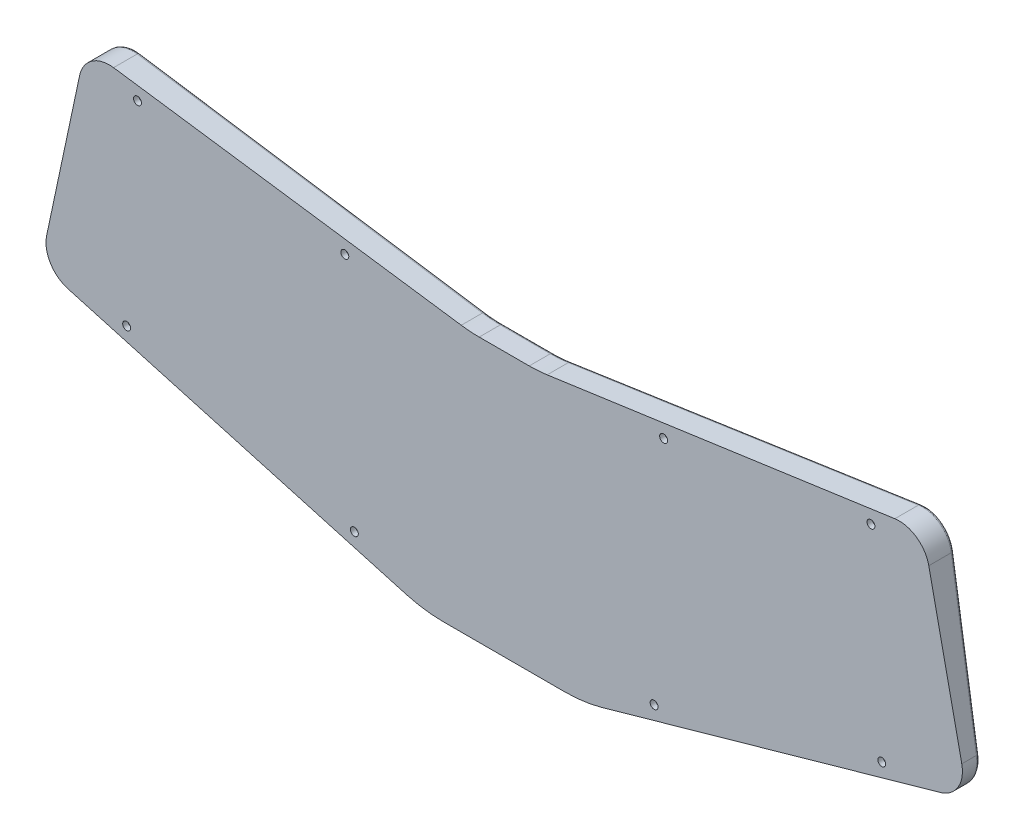
SolidWorks part; units mm, degrees
ref_plane "Front Plane" through (0, 0, 0) normal (0, 0, 1) x (1, 0, 0)
ref_plane "Top Plane" through (0, 0, 0) normal (0, 1, 0) x (1, 0, 0)
ref_plane "Right Plane" through (0, 0, 0) normal (1, 0, 0) x (0, 0, -1)
sketch "Model" plane through (0, 0, 0) normal (0, 0, 1) x (1, 0, 0)
  line L0 (7.1929, 63.9009) -> (19.4198, 61.302)
  line L1 (19.9974, 60.4125) -> (17.3986, 48.1856)
  line L2 (16.509, 47.6079) -> (4.2822, 50.2068)
  line L3 (3.7045, 51.0964) -> (6.3034, 63.3232)
  line L4 (3.2426, 45.3161) -> (15.4694, 42.7172)
  line L5 (16.0471, 41.8276) -> (13.4482, 29.6008)
  line L6 (12.5587, 29.0231) -> (0.3318, 31.622)
  line L7 (-0.2458, 32.5116) -> (2.3531, 44.7384)
  line L8 (-0.7077, 26.7313) -> (11.5191, 24.1324)
  line L9 (12.0968, 23.2428) -> (9.4979, 11.016)
  line L10 (8.6084, 10.4383) -> (-3.6185, 13.0372)
  line L11 (-4.1962, 13.9268) -> (-1.5973, 26.1536)
  line L12 (26.1936, 61.9069) -> (38.4204, 59.308)
  line L13 (38.9981, 58.4184) -> (36.3992, 46.1916)
  line L14 (35.5096, 45.6139) -> (23.2828, 48.2128)
  line L15 (22.7051, 49.1023) -> (25.304, 61.3292)
  line L16 (22.2432, 43.3221) -> (34.4701, 40.7232)
  line L17 (35.0478, 39.8336) -> (32.4489, 27.6068)
  line L18 (31.5593, 27.0291) -> (19.3325, 29.628)
  line L19 (18.7548, 30.5175) -> (21.3537, 42.7444)
  line L20 (18.2929, 24.7373) -> (30.5198, 22.1384)
  line L21 (31.0974, 21.2488) -> (28.4985, 9.022)
  line L22 (27.609, 8.4443) -> (15.3821, 11.0432)
  line L23 (14.8045, 11.9327) -> (17.4034, 24.1596)
  line L24 (45.2981, 60.4019) -> (57.525, 57.803)
  line L25 (58.1027, 56.9135) -> (55.5038, 44.6866)
  line L26 (54.6142, 44.109) -> (42.3874, 46.7078)
  line L27 (41.8097, 47.5974) -> (44.4086, 59.8242)
  line L28 (41.3478, 41.8171) -> (53.5747, 39.2182)
  line L29 (54.1523, 38.3287) -> (51.5534, 26.1018)
  line L30 (50.6639, 25.5241) -> (38.4371, 28.123)
  line L31 (37.8594, 29.0126) -> (40.4583, 41.2394)
  line L32 (37.3975, 23.2323) -> (49.6243, 20.6334)
  line L33 (50.202, 19.7439) -> (47.6031, 7.517)
  line L34 (46.7136, 6.9393) -> (34.4867, 9.5382)
  line L35 (33.9091, 10.4278) -> (36.5079, 22.6546)
  line L36 (64.4027, 58.897) -> (76.6296, 56.2981)
  line L37 (77.2072, 55.4085) -> (74.6083, 43.1817)
  line L38 (73.7188, 42.604) -> (61.492, 45.2029)
  line L39 (60.9143, 46.0924) -> (63.5132, 58.3193)
  line L40 (60.4524, 40.3122) -> (72.6792, 37.7133)
  line L41 (73.2569, 36.8237) -> (70.658, 24.5969)
  line L42 (69.7685, 24.0192) -> (57.5416, 26.6181)
  line L43 (56.964, 27.5076) -> (59.5629, 39.7345)
  line L44 (56.5021, 21.7274) -> (68.7289, 19.1285)
  line L45 (69.3066, 18.2389) -> (66.7077, 6.0121)
  line L46 (65.8182, 5.4344) -> (53.5913, 8.0333)
  line L47 (53.0136, 8.9228) -> (55.6125, 21.1497)
  line L48 (52.5518, 3.1425) -> (64.7786, 0.5437)
  line L49 (65.3563, -0.3459) -> (62.7574, -12.5727)
  line L50 (61.8678, -13.1504) -> (49.641, -10.5515)
  line L51 (49.0633, -9.662) -> (51.6622, 2.5649)
  line L52 (82.4677, 52.5013) -> (94.6946, 49.9024)
  line L53 (95.2723, 49.0128) -> (92.6734, 36.786)
  line L54 (91.7838, 36.2083) -> (79.557, 38.8072)
  line L55 (78.9793, 39.6967) -> (81.5782, 51.9236)
  line L56 (78.5174, 33.9165) -> (90.7443, 31.3176)
  line L57 (91.3219, 30.428) -> (88.723, 18.2012)
  line L58 (87.8335, 17.6235) -> (75.6067, 20.2224)
  line L59 (75.029, 21.1119) -> (77.6279, 33.3388)
  line L60 (74.5671, 15.3317) -> (86.7939, 12.7328)
  line L61 (87.3716, 11.8432) -> (84.7727, -0.3836)
  line L62 (83.8832, -0.9613) -> (71.6563, 1.6376)
  line L63 (71.0787, 2.5271) -> (73.6776, 14.754)
  line L64 (101.4684, 50.5072) -> (113.6952, 47.9083)
  line L65 (114.2729, 47.0188) -> (111.674, 34.792)
  line L66 (110.7845, 34.2143) -> (98.5576, 36.8132)
  line L67 (97.9799, 37.7027) -> (100.5788, 49.9296)
  line L68 (97.5181, 31.9224) -> (109.7449, 29.3235)
  line L69 (110.3226, 28.434) -> (107.7237, 16.2072)
  line L70 (106.8341, 15.6295) -> (94.6073, 18.2284)
  line L71 (94.0296, 19.1179) -> (96.6285, 31.3448)
  line L72 (93.5677, 13.3376) -> (105.7946, 10.7387)
  line L73 (106.3723, 9.8492) -> (103.7734, -2.3777)
  line L74 (102.8838, -2.9553) -> (90.657, -0.3564)
  line L75 (90.0793, 0.5331) -> (92.6782, 12.76)
  line L76 (134.1052, 48.9374) -> (131.5063, 36.7105)
  line L77 (130.6167, 36.1328) -> (118.3899, 38.7317)
  line L78 (117.8122, 39.6213) -> (120.4111, 51.8481)
  line L79 (117.3503, 33.841) -> (129.5772, 31.2421)
  line L80 (130.1548, 30.3526) -> (127.556, 18.1257)
  line L81 (126.6664, 17.548) -> (114.4396, 20.1469)
  line L82 (113.8619, 21.0365) -> (116.4608, 33.2633)
  line L83 (113.4, 15.2562) -> (125.6268, 12.6573)
  line L84 (126.2045, 11.7678) -> (123.6056, -0.4591)
  line L85 (122.7161, -1.0368) -> (110.4892, 1.5621)
  line L86 (109.9116, 2.4517) -> (112.5105, 14.6785)
  line L87 (70.6168, -3.2531) -> (82.8436, -5.852)
  line L88 (83.4213, -6.7416) -> (80.8224, -18.9684)
  line L89 (79.9329, -19.5461) -> (67.706, -16.9472)
  line L90 (67.1283, -16.0577) -> (69.7272, -3.8308)
  line L91 (89.6174, -5.2472) -> (101.8443, -7.8461)
  line L92 (102.4219, -8.7356) -> (99.823, -20.9625)
  line L93 (98.9335, -21.5401) -> (86.7066, -18.9412)
  line L94 (86.129, -18.0517) -> (88.7279, -5.8248)
  line L95 (117.654, -29.3648) -> (112.0852, -26.5274)
  line L96 (111.7574, -25.5186) -> (117.4323, -14.381)
  line L97 (118.4411, -14.0533) -> (129.5787, -19.7282)
  line L98 (129.9064, -20.7369) -> (124.2315, -31.8745)
  line L99 (123.2228, -32.2023) -> (117.654, -29.3648)
  line L100 (112.629, -33.5493) -> (124.2783, -36.8388)
  line L101 (137.0504, -38.6074) -> (160.1264, -38.6074)
  line L102 (160.1264, -38.6074) -> (183.2025, -38.6074)
  line L103 (195.9746, -36.8388) -> (207.6239, -33.5493)
  line L104 (226.4824, -28.2242) -> (271.949, -15.3856)
  line L105 (271.949, -15.3856) -> (293.9202, -9.1816)
  line L106 (210.7632, 57.9332) -> (177.0346, 53.1572)
  line L107 (169.604, 52.6338) -> (150.6488, 52.6338)
  line L108 (143.2182, 53.1572) -> (109.4896, 57.9332)
  line L109 (90.0873, 60.6806) -> (30.9176, 69.0589)
  line L110 (289.3352, 69.0589) -> (230.1656, 60.6806)
  line L111 (26.3327, -9.1816) -> (48.3039, -15.3856)
  line L112 (48.3039, -15.3856) -> (93.7705, -28.2242)
  line L113 (312.7787, -3.8564) -> (324.1811, -0.6367)
  line L114 (-2.1254, 39.3007) -> (3.622, 66.34)
  line L115 (-2.1254, 39.3007) -> (-8.8731, 7.5553)
  line L116 (13.8071, 71.4818) -> (11.4504, 71.8155)
  line L117 (-3.9283, -0.6367) -> (7.4742, -3.8564)
  line L118 (306.4458, 71.4818) -> (308.8024, 71.8155)
  line L119 (322.3782, 39.3007) -> (329.1259, 7.5553)
  line L120 (322.3782, 39.3007) -> (316.6308, 66.34)
  line L121 (121.3006, 52.4258) -> (133.5275, 49.8269)
  line L122 (313.0599, 63.9009) -> (300.8331, 61.302)
  line L123 (300.2554, 60.4125) -> (302.8543, 48.1856)
  line L124 (303.7438, 47.6079) -> (315.9707, 50.2068)
  line L125 (316.5483, 51.0964) -> (313.9494, 63.3232)
  line L126 (317.0102, 45.3161) -> (304.7834, 42.7172)
  line L127 (304.2057, 41.8276) -> (306.8046, 29.6008)
  line L128 (307.6941, 29.0231) -> (319.921, 31.622)
  line L129 (320.4987, 32.5116) -> (317.8998, 44.7384)
  line L130 (320.9605, 26.7313) -> (308.7337, 24.1324)
  line L131 (308.156, 23.2428) -> (310.7549, 11.016)
  line L132 (311.6445, 10.4383) -> (323.8713, 13.0372)
  line L133 (324.449, 13.9268) -> (321.8501, 26.1536)
  line L134 (294.0593, 61.9069) -> (281.8324, 59.308)
  line L135 (281.2548, 58.4184) -> (283.8536, 46.1916)
  line L136 (284.7432, 45.6139) -> (296.97, 48.2128)
  line L137 (297.5477, 49.1023) -> (294.9488, 61.3292)
  line L138 (298.0096, 43.3221) -> (285.7828, 40.7232)
  line L139 (285.2051, 39.8336) -> (287.804, 27.6068)
  line L140 (288.6935, 27.0291) -> (300.9204, 29.628)
  line L141 (301.498, 30.5175) -> (298.8991, 42.7444)
  line L142 (301.9599, 24.7373) -> (289.7331, 22.1384)
  line L143 (289.1554, 21.2488) -> (291.7543, 9.022)
  line L144 (292.6438, 8.4443) -> (304.8707, 11.0432)
  line L145 (305.4484, 11.9327) -> (302.8495, 24.1596)
  line L146 (274.9547, 60.4019) -> (262.7278, 57.803)
  line L147 (262.1502, 56.9135) -> (264.7491, 44.6866)
  line L148 (265.6386, 44.109) -> (277.8655, 46.7078)
  line L149 (278.4431, 47.5974) -> (275.8442, 59.8242)
  line L150 (278.905, 41.8171) -> (266.6782, 39.2182)
  line L151 (266.1005, 38.3287) -> (268.6994, 26.1018)
  line L152 (269.5889, 25.5241) -> (281.8158, 28.123)
  line L153 (282.3935, 29.0126) -> (279.7946, 41.2394)
  line L154 (282.8553, 23.2323) -> (270.6285, 20.6334)
  line L155 (270.0508, 19.7439) -> (272.6497, 7.517)
  line L156 (273.5393, 6.9393) -> (285.7661, 9.5382)
  line L157 (286.3438, 10.4278) -> (283.7449, 22.6546)
  line L158 (255.8501, 58.897) -> (243.6233, 56.2981)
  line L159 (243.0456, 55.4085) -> (245.6445, 43.1817)
  line L160 (246.534, 42.604) -> (258.7609, 45.2029)
  line L161 (259.3385, 46.0924) -> (256.7397, 58.3193)
  line L162 (259.8004, 40.3122) -> (247.5736, 37.7133)
  line L163 (246.9959, 36.8237) -> (249.5948, 24.5969)
  line L164 (250.4843, 24.0192) -> (262.7112, 26.6181)
  line L165 (263.2889, 27.5076) -> (260.69, 39.7345)
  line L166 (263.7508, 21.7274) -> (251.5239, 19.1285)
  line L167 (250.9462, 18.2389) -> (253.5451, 6.0121)
  line L168 (254.4347, 5.4344) -> (266.6615, 8.0333)
  line L169 (267.2392, 8.9228) -> (264.6403, 21.1497)
  line L170 (267.7011, 3.1425) -> (255.4742, 0.5437)
  line L171 (254.8966, -0.3459) -> (257.4954, -12.5727)
  line L172 (258.385, -13.1504) -> (270.6118, -10.5515)
  line L173 (271.1895, -9.662) -> (268.5906, 2.5649)
  line L174 (237.7851, 52.5013) -> (225.5582, 49.9024)
  line L175 (224.9806, 49.0128) -> (227.5795, 36.786)
  line L176 (228.469, 36.2083) -> (240.6958, 38.8072)
  line L177 (241.2735, 39.6967) -> (238.6746, 51.9236)
  line L178 (241.7354, 33.9165) -> (229.5086, 31.3176)
  line L179 (228.9309, 30.428) -> (231.5298, 18.2012)
  line L180 (232.4193, 17.6235) -> (244.6462, 20.2224)
  line L181 (245.2238, 21.1119) -> (242.6249, 33.3388)
  line L182 (245.6857, 15.3317) -> (233.4589, 12.7328)
  line L183 (232.8812, 11.8432) -> (235.4801, -0.3836)
  line L184 (236.3696, -0.9613) -> (248.5965, 1.6376)
  line L185 (249.1742, 2.5271) -> (246.5753, 14.754)
  line L186 (218.7845, 50.5072) -> (206.5576, 47.9083)
  line L187 (205.9799, 47.0188) -> (208.5788, 34.792)
  line L188 (209.4684, 34.2143) -> (221.6952, 36.8132)
  line L189 (222.2729, 37.7027) -> (219.674, 49.9296)
  line L190 (222.7348, 31.9224) -> (210.5079, 29.3235)
  line L191 (209.9303, 28.434) -> (212.5292, 16.2072)
  line L192 (213.4187, 15.6295) -> (225.6455, 18.2284)
  line L193 (226.2232, 19.1179) -> (223.6243, 31.3448)
  line L194 (226.6851, 13.3376) -> (214.4583, 10.7387)
  line L195 (213.8806, 9.8492) -> (216.4795, -2.3777)
  line L196 (217.369, -2.9553) -> (229.5959, -0.3564)
  line L197 (230.1735, 0.5331) -> (227.5746, 12.76)
  line L198 (186.1477, 48.9374) -> (188.7466, 36.7105)
  line L199 (189.6361, 36.1328) -> (201.8629, 38.7317)
  line L200 (202.4406, 39.6213) -> (199.8417, 51.8481)
  line L201 (202.9025, 33.841) -> (190.6757, 31.2421)
  line L202 (190.098, 30.3526) -> (192.6969, 18.1257)
  line L203 (193.5864, 17.548) -> (205.8133, 20.1469)
  line L204 (206.3909, 21.0365) -> (203.792, 33.2633)
  line L205 (206.8528, 15.2562) -> (194.626, 12.6573)
  line L206 (194.0483, 11.7678) -> (196.6472, -0.4591)
  line L207 (197.5367, -1.0368) -> (209.7636, 1.5621)
  line L208 (210.3413, 2.4517) -> (207.7424, 14.6785)
  line L209 (249.636, -3.2531) -> (237.4092, -5.852)
  line L210 (236.8315, -6.7416) -> (239.4304, -18.9684)
  line L211 (240.32, -19.5461) -> (252.5468, -16.9472)
  line L212 (253.1245, -16.0577) -> (250.5256, -3.8308)
  line L213 (230.6354, -5.2472) -> (218.4086, -7.8461)
  line L214 (217.8309, -8.7356) -> (220.4298, -20.9625)
  line L215 (221.3193, -21.5401) -> (233.5462, -18.9412)
  line L216 (234.1239, -18.0517) -> (231.525, -5.8248)
  line L217 (202.5988, -29.3648) -> (208.1676, -26.5274)
  line L218 (208.4954, -25.5186) -> (202.8205, -14.381)
  line L219 (201.8118, -14.0533) -> (190.6742, -19.7282)
  line L220 (190.3464, -20.7369) -> (196.0213, -31.8745)
  line L221 (197.03, -32.2023) -> (202.5988, -29.3648)
  line L222 (198.9522, 52.4258) -> (186.7253, 49.8269)
  line L223 (169.604, 55.6338) -> (150.6488, 55.6338)
  line L224 (143.6388, 56.1276) -> (11.8711, 74.7858)
  line L225 (0.6876, 66.9637) -> (-5.0598, 39.9244)
  line L226 (-5.0598, 39.9244) -> (-11.8075, 8.179)
  line L227 (-4.7435, -3.5238) -> (47.4886, -18.2727)
  line L228 (47.4886, -18.2727) -> (123.463, -39.7259)
  line L229 (137.0504, -41.6074) -> (160.1264, -41.6074)
  line L230 (160.1264, -41.6074) -> (183.2025, -41.6074)
  line L231 (196.7898, -39.7259) -> (272.7642, -18.2727)
  line L232 (272.7642, -18.2727) -> (324.9963, -3.5238)
  line L233 (332.0603, 8.179) -> (325.3126, 39.9244)
  line L234 (325.3126, 39.9244) -> (319.5653, 66.9637)
  line L235 (308.3818, 74.7858) -> (176.614, 56.1276)
  line L236 (169.604, 57.1338) -> (150.6488, 57.1338)
  line L237 (143.8491, 57.6128) -> (12.0814, 76.271)
  line L238 (-0.7797, 67.2756) -> (-6.527, 40.2363)
  line L239 (-6.527, 40.2363) -> (-13.2747, 8.4909)
  line L240 (-5.1511, -4.9673) -> (47.081, -19.7163)
  line L241 (47.081, -19.7163) -> (123.0554, -41.1694)
  line L242 (137.0504, -43.1074) -> (160.1264, -43.1074)
  line L243 (160.1264, -43.1074) -> (183.2025, -43.1074)
  line L244 (197.1974, -41.1694) -> (273.1718, -19.7163)
  line L245 (273.1718, -19.7163) -> (325.404, -4.9673)
  line L246 (333.5276, 8.4909) -> (326.7799, 40.2363)
  line L247 (326.7799, 40.2363) -> (321.0325, 67.2756)
  line L248 (308.1715, 76.271) -> (176.4037, 57.6128)
  arc A0 (106.6702, -28.8979) -> (101.2821, -27.3764) centre (103.1997, -30.8868) ccw
  arc A1 (93.7705, -28.2242) -> (101.2821, -27.3764) centre (96.4879, -18.6005) ccw
  arc A2 (106.6702, -28.8979) -> (112.629, -33.5493) centre (115.3464, -23.9256) ccw
  circle A3 centre (103.3356, -30.4056) radius 1.5
  arc A4 (207.6239, -33.5493) -> (213.5826, -28.8979) centre (204.9064, -23.9256) ccw
  arc A5 (218.9708, -27.3764) -> (226.4824, -28.2242) centre (223.7649, -18.6005) ccw
  arc A6 (218.9708, -27.3764) -> (213.5826, -28.8979) centre (217.0531, -30.8868) ccw
  circle A7 centre (216.9173, -30.4056) radius 1.5
  arc A8 (218.0932, 56.0855) -> (223.6367, 56.8704) centre (220.4644, 59.3069) ccw
  arc A9 (96.6161, 56.8704) -> (102.1596, 56.0855) centre (99.7884, 59.3069) ccw
  arc A10 (109.4896, 57.9332) -> (102.1596, 56.0855) centre (108.0876, 48.032) ccw
  arc A11 (96.6161, 56.8704) -> (90.0873, 60.6806) centre (88.6852, 50.7793) ccw
  arc A12 (218.0932, 56.0855) -> (210.7632, 57.9332) centre (212.1652, 48.032) ccw
  arc A13 (230.1656, 60.6806) -> (223.6367, 56.8704) centre (231.5676, 50.7793) ccw
  circle A14 centre (99.7183, 58.8118) radius 1.5
  circle A15 centre (220.5345, 58.8118) radius 1.5
  arc A16 (305.2671, -3.0086) -> (299.8789, -4.5301) centre (303.3494, -6.519) ccw
  arc A17 (20.3739, -4.5301) -> (14.9858, -3.0086) centre (16.9034, -6.519) ccw
  arc A18 (20.3739, -4.5301) -> (26.3327, -9.1816) centre (29.0501, 0.4421) ccw
  arc A19 (305.2671, -3.0086) -> (312.7787, -3.8564) centre (310.0612, 5.7673) ccw
  arc A20 (293.9202, -9.1816) -> (299.8789, -4.5301) centre (291.2027, 0.4421) ccw
  arc A21 (7.4742, -3.8564) -> (14.9858, -3.0086) centre (10.1916, 5.7673) ccw
  circle A22 centre (17.0393, -6.0378) radius 1.5
  circle A23 centre (303.2135, -6.0378) radius 1.5
  arc A24 (-8.8731, 7.5553) -> (-3.9283, -0.6367) centre (-2.026, 6.0999) ccw
  arc A25 (11.4504, 71.8155) -> (3.622, 66.34) centre (10.469, 64.8846) ccw
  arc A26 (316.6308, 66.34) -> (308.8024, 71.8155) centre (309.7838, 64.8846) ccw
  arc A27 (324.1811, -0.6367) -> (329.1259, 7.5553) centre (322.2789, 6.0999) ccw
  arc A28 (296.6652, 67.2112) -> (302.641, 68.6986) centre (299.0364, 70.4326) ccw
  arc A29 (17.6118, 68.6986) -> (23.5876, 67.2112) centre (21.2165, 70.4326) ccw
  arc A30 (30.9176, 69.0589) -> (23.5876, 67.2112) centre (29.5156, 59.1577) ccw
  arc A31 (17.6118, 68.6986) -> (13.8071, 71.4818) centre (13.106, 66.5312) ccw
  arc A32 (306.4458, 71.4818) -> (302.641, 68.6986) centre (307.1468, 66.5312) ccw
  arc A33 (296.6652, 67.2112) -> (289.3352, 69.0589) centre (290.7372, 59.1577) ccw
  circle A34 centre (299.1065, 69.9376) radius 1.5
  circle A35 centre (21.1464, 69.9376) radius 1.5
  arc A36 (3.7045, 51.0964) -> (4.2822, 50.2068) centre (4.4381, 50.9404) ccw
  arc A37 (7.1929, 63.9009) -> (6.3034, 63.3232) centre (7.037, 63.1673) ccw
  arc A38 (19.9974, 60.4125) -> (19.4198, 61.302) centre (19.2638, 60.5684) ccw
  arc A39 (16.509, 47.6079) -> (17.3986, 48.1856) centre (16.6649, 48.3415) ccw
  arc A40 (3.2426, 45.3161) -> (2.3531, 44.7384) centre (3.0867, 44.5825) ccw
  arc A41 (-0.2458, 32.5116) -> (0.3318, 31.622) centre (0.4878, 32.3556) ccw
  arc A42 (12.5587, 29.0231) -> (13.4482, 29.6008) centre (12.7146, 29.7567) ccw
  arc A43 (16.0471, 41.8276) -> (15.4694, 42.7172) centre (15.3135, 41.9836) ccw
  arc A44 (-0.7077, 26.7313) -> (-1.5973, 26.1536) centre (-0.8637, 25.9977) ccw
  arc A45 (-4.1962, 13.9268) -> (-3.6185, 13.0372) centre (-3.4625, 13.7708) ccw
  arc A46 (8.6084, 10.4383) -> (9.4979, 11.016) centre (8.7643, 11.1719) ccw
  arc A47 (12.0968, 23.2428) -> (11.5191, 24.1324) centre (11.3632, 23.3988) ccw
  arc A48 (14.8045, 11.9327) -> (15.3821, 11.0432) centre (15.5381, 11.7768) ccw
  arc A49 (27.609, 8.4443) -> (28.4985, 9.022) centre (27.7649, 9.1779) ccw
  arc A50 (31.0974, 21.2488) -> (30.5198, 22.1384) centre (30.3638, 21.4048) ccw
  arc A51 (18.2929, 24.7373) -> (17.4034, 24.1596) centre (18.137, 24.0036) ccw
  arc A52 (18.7548, 30.5175) -> (19.3325, 29.628) centre (19.4884, 30.3616) ccw
  arc A53 (31.5593, 27.0291) -> (32.4489, 27.6068) centre (31.7152, 27.7627) ccw
  arc A54 (35.0478, 39.8336) -> (34.4701, 40.7232) centre (34.3141, 39.9896) ccw
  arc A55 (22.2432, 43.3221) -> (21.3537, 42.7444) centre (22.0873, 42.5885) ccw
  arc A56 (22.7051, 49.1023) -> (23.2828, 48.2128) centre (23.4387, 48.9464) ccw
  arc A57 (35.5096, 45.6139) -> (36.3992, 46.1916) centre (35.6656, 46.3475) ccw
  arc A58 (38.9981, 58.4184) -> (38.4204, 59.308) centre (38.2645, 58.5744) ccw
  arc A59 (26.1936, 61.9069) -> (25.304, 61.3292) centre (26.0376, 61.1733) ccw
  arc A60 (33.9091, 10.4278) -> (34.4867, 9.5382) centre (34.6427, 10.2718) ccw
  arc A61 (37.3975, 23.2323) -> (36.5079, 22.6546) centre (37.2416, 22.4987) ccw
  arc A62 (50.202, 19.7439) -> (49.6243, 20.6334) centre (49.4684, 19.8998) ccw
  arc A63 (46.7136, 6.9393) -> (47.6031, 7.517) centre (46.8695, 7.673) ccw
  arc A64 (50.6639, 25.5241) -> (51.5534, 26.1018) centre (50.8198, 26.2578) ccw
  arc A65 (37.8594, 29.0126) -> (38.4371, 28.123) centre (38.593, 28.8567) ccw
  arc A66 (41.3478, 41.8171) -> (40.4583, 41.2394) centre (41.1919, 41.0835) ccw
  arc A67 (54.1523, 38.3287) -> (53.5747, 39.2182) centre (53.4187, 38.4846) ccw
  arc A68 (54.6142, 44.109) -> (55.5038, 44.6866) centre (54.7702, 44.8426) ccw
  arc A69 (41.8097, 47.5974) -> (42.3874, 46.7078) centre (42.5433, 47.4415) ccw
  arc A70 (45.2981, 60.4019) -> (44.4086, 59.8242) centre (45.1422, 59.6683) ccw
  arc A71 (58.1027, 56.9135) -> (57.525, 57.803) centre (57.369, 57.0694) ccw
  arc A72 (56.964, 27.5076) -> (57.5416, 26.6181) centre (57.6976, 27.3517) ccw
  arc A73 (60.4524, 40.3122) -> (59.5629, 39.7345) centre (60.2965, 39.5785) ccw
  arc A74 (73.2569, 36.8237) -> (72.6792, 37.7133) centre (72.5233, 36.9797) ccw
  arc A75 (69.7685, 24.0192) -> (70.658, 24.5969) centre (69.9244, 24.7528) ccw
  arc A76 (60.9143, 46.0924) -> (61.492, 45.2029) centre (61.6479, 45.9365) ccw
  arc A77 (73.7188, 42.604) -> (74.6083, 43.1817) centre (73.8747, 43.3376) ccw
  arc A78 (77.2072, 55.4085) -> (76.6296, 56.2981) centre (76.4736, 55.5645) ccw
  arc A79 (64.4027, 58.897) -> (63.5132, 58.3193) centre (64.2468, 58.1634) ccw
  arc A80 (53.0136, 8.9228) -> (53.5913, 8.0333) centre (53.7472, 8.7669) ccw
  arc A81 (56.5021, 21.7274) -> (55.6125, 21.1497) centre (56.3461, 20.9937) ccw
  arc A82 (69.3066, 18.2389) -> (68.7289, 19.1285) centre (68.573, 18.3948) ccw
  arc A83 (65.8182, 5.4344) -> (66.7077, 6.0121) centre (65.9741, 6.168) ccw
  arc A84 (49.0633, -9.662) -> (49.641, -10.5515) centre (49.7969, -9.8179) ccw
  arc A85 (52.5518, 3.1425) -> (51.6622, 2.5649) centre (52.3958, 2.4089) ccw
  arc A86 (65.3563, -0.3459) -> (64.7786, 0.5437) centre (64.6227, -0.19) ccw
  arc A87 (61.8678, -13.1504) -> (62.7574, -12.5727) centre (62.0238, -12.4168) ccw
  arc A88 (67.1283, -16.0577) -> (67.706, -16.9472) centre (67.8619, -16.2136) ccw
  arc A89 (70.6168, -3.2531) -> (69.7272, -3.8308) centre (70.4608, -3.9868) ccw
  arc A90 (83.4213, -6.7416) -> (82.8436, -5.852) centre (82.6877, -6.5856) ccw
  arc A91 (79.9329, -19.5461) -> (80.8224, -18.9684) centre (80.0888, -18.8125) ccw
  arc A92 (71.0787, 2.5271) -> (71.6563, 1.6376) centre (71.8123, 2.3712) ccw
  arc A93 (83.8832, -0.9613) -> (84.7727, -0.3836) centre (84.0391, -0.2277) ccw
  arc A94 (87.3716, 11.8432) -> (86.7939, 12.7328) centre (86.638, 11.9992) ccw
  arc A95 (74.5671, 15.3317) -> (73.6776, 14.754) centre (74.4112, 14.5981) ccw
  arc A96 (75.029, 21.1119) -> (75.6067, 20.2224) centre (75.7626, 20.956) ccw
  arc A97 (87.8335, 17.6235) -> (88.723, 18.2012) centre (87.9894, 18.3571) ccw
  arc A98 (91.3219, 30.428) -> (90.7443, 31.3176) centre (90.5883, 30.584) ccw
  arc A99 (78.5174, 33.9165) -> (77.6279, 33.3388) centre (78.3615, 33.1829) ccw
  arc A100 (78.9793, 39.6967) -> (79.557, 38.8072) centre (79.7129, 39.5408) ccw
  arc A101 (82.4677, 52.5013) -> (81.5782, 51.9236) centre (82.3118, 51.7677) ccw
  arc A102 (95.2723, 49.0128) -> (94.6946, 49.9024) centre (94.5387, 49.1688) ccw
  arc A103 (91.7838, 36.2083) -> (92.6734, 36.786) centre (91.9398, 36.9419) ccw
  arc A104 (97.9799, 37.7027) -> (98.5576, 36.8132) centre (98.7135, 37.5468) ccw
  arc A105 (101.4684, 50.5072) -> (100.5788, 49.9296) centre (101.3124, 49.7736) ccw
  arc A106 (114.2729, 47.0188) -> (113.6952, 47.9083) centre (113.5393, 47.1747) ccw
  arc A107 (110.7845, 34.2143) -> (111.674, 34.792) centre (110.9404, 34.9479) ccw
  arc A108 (97.5181, 31.9224) -> (96.6285, 31.3448) centre (97.3621, 31.1888) ccw
  arc A109 (110.3226, 28.434) -> (109.7449, 29.3235) centre (109.589, 28.5899) ccw
  arc A110 (106.8341, 15.6295) -> (107.7237, 16.2072) centre (106.9901, 16.3631) ccw
  arc A111 (94.0296, 19.1179) -> (94.6073, 18.2284) centre (94.7632, 18.962) ccw
  arc A112 (93.5677, 13.3376) -> (92.6782, 12.76) centre (93.4118, 12.604) ccw
  arc A113 (106.3723, 9.8492) -> (105.7946, 10.7387) centre (105.6386, 10.0051) ccw
  arc A114 (102.8838, -2.9553) -> (103.7734, -2.3777) centre (103.0397, -2.2217) ccw
  arc A115 (90.0793, 0.5331) -> (90.657, -0.3564) centre (90.8129, 0.3772) ccw
  arc A116 (89.6174, -5.2472) -> (88.7279, -5.8248) centre (89.4615, -5.9808) ccw
  arc A117 (102.4219, -8.7356) -> (101.8443, -7.8461) centre (101.6883, -8.5797) ccw
  arc A118 (98.9335, -21.5401) -> (99.823, -20.9625) centre (99.0894, -20.8065) ccw
  arc A119 (86.129, -18.0517) -> (86.7066, -18.9412) centre (86.8626, -18.2076) ccw
  arc A120 (111.7574, -25.5186) -> (112.0852, -26.5274) centre (112.4257, -25.8591) ccw
  arc A121 (118.4411, -14.0533) -> (117.4323, -14.381) centre (118.1006, -14.7215) ccw
  arc A122 (129.9064, -20.7369) -> (129.5787, -19.7282) centre (129.2382, -20.3964) ccw
  arc A123 (123.2228, -32.2023) -> (124.2315, -31.8745) centre (123.5633, -31.534) ccw
  arc A124 (109.9116, 2.4517) -> (110.4892, 1.5621) centre (110.6452, 2.2957) ccw
  arc A125 (122.7161, -1.0368) -> (123.6056, -0.4591) centre (122.872, -0.3032) ccw
  arc A126 (126.2045, 11.7678) -> (125.6268, 12.6573) centre (125.4709, 11.9237) ccw
  arc A127 (113.4, 15.2562) -> (112.5105, 14.6785) centre (113.2441, 14.5226) ccw
  arc A128 (113.8619, 21.0365) -> (114.4396, 20.1469) centre (114.5955, 20.8805) ccw
  arc A129 (126.6664, 17.548) -> (127.556, 18.1257) centre (126.8223, 18.2817) ccw
  arc A130 (130.1548, 30.3526) -> (129.5772, 31.2421) centre (129.4212, 30.5085) ccw
  arc A131 (117.3503, 33.841) -> (116.4608, 33.2633) centre (117.1944, 33.1074) ccw
  arc A132 (117.8122, 39.6213) -> (118.3899, 38.7317) centre (118.5458, 39.4654) ccw
  arc A133 (130.6167, 36.1328) -> (131.5063, 36.7105) centre (130.7727, 36.8665) ccw
  arc A134 (134.1052, 48.9374) -> (133.5275, 49.8269) centre (133.3716, 49.0933) ccw
  arc A135 (121.3006, 52.4258) -> (120.4111, 51.8481) centre (121.1447, 51.6922) ccw
  arc A136 (313.9494, 63.3232) -> (313.0599, 63.9009) centre (313.2158, 63.1673) ccw
  arc A137 (300.8331, 61.302) -> (300.2554, 60.4125) centre (300.989, 60.5684) ccw
  arc A138 (302.8543, 48.1856) -> (303.7438, 47.6079) centre (303.5879, 48.3415) ccw
  arc A139 (315.9707, 50.2068) -> (316.5483, 51.0964) centre (315.8147, 50.9404) ccw
  arc A140 (317.8998, 44.7384) -> (317.0102, 45.3161) centre (317.1662, 44.5825) ccw
  arc A141 (304.7834, 42.7172) -> (304.2057, 41.8276) centre (304.9393, 41.9836) ccw
  arc A142 (306.8046, 29.6008) -> (307.6941, 29.0231) centre (307.5382, 29.7567) ccw
  arc A143 (319.921, 31.622) -> (320.4987, 32.5116) centre (319.7651, 32.3556) ccw
  arc A144 (321.8501, 26.1536) -> (320.9605, 26.7313) centre (321.1165, 25.9977) ccw
  arc A145 (308.7337, 24.1324) -> (308.156, 23.2428) centre (308.8896, 23.3988) ccw
  arc A146 (310.7549, 11.016) -> (311.6445, 10.4383) centre (311.4885, 11.1719) ccw
  arc A147 (323.8713, 13.0372) -> (324.449, 13.9268) centre (323.7154, 13.7708) ccw
  arc A148 (294.9488, 61.3292) -> (294.0593, 61.9069) centre (294.2152, 61.1733) ccw
  arc A149 (281.8324, 59.308) -> (281.2548, 58.4184) centre (281.9884, 58.5744) ccw
  arc A150 (283.8536, 46.1916) -> (284.7432, 45.6139) centre (284.5873, 46.3475) ccw
  arc A151 (296.97, 48.2128) -> (297.5477, 49.1023) centre (296.8141, 48.9464) ccw
  arc A152 (298.8991, 42.7444) -> (298.0096, 43.3221) centre (298.1655, 42.5885) ccw
  arc A153 (285.7828, 40.7232) -> (285.2051, 39.8336) centre (285.9387, 39.9896) ccw
  arc A154 (287.804, 27.6068) -> (288.6935, 27.0291) centre (288.5376, 27.7627) ccw
  arc A155 (300.9204, 29.628) -> (301.498, 30.5175) centre (300.7644, 30.3616) ccw
  arc A156 (302.8495, 24.1596) -> (301.9599, 24.7373) centre (302.1159, 24.0036) ccw
  arc A157 (289.7331, 22.1384) -> (289.1554, 21.2488) centre (289.889, 21.4048) ccw
  arc A158 (291.7543, 9.022) -> (292.6438, 8.4443) centre (292.4879, 9.1779) ccw
  arc A159 (304.8707, 11.0432) -> (305.4484, 11.9327) centre (304.7147, 11.7768) ccw
  arc A160 (262.7278, 57.803) -> (262.1502, 56.9135) centre (262.8838, 57.0694) ccw
  arc A161 (275.8442, 59.8242) -> (274.9547, 60.4019) centre (275.1106, 59.6683) ccw
  arc A162 (264.7491, 44.6866) -> (265.6386, 44.109) centre (265.4827, 44.8426) ccw
  arc A163 (277.8655, 46.7078) -> (278.4431, 47.5974) centre (277.7095, 47.4415) ccw
  arc A164 (266.6782, 39.2182) -> (266.1005, 38.3287) centre (266.8341, 38.4846) ccw
  arc A165 (279.7946, 41.2394) -> (278.905, 41.8171) centre (279.0609, 41.0835) ccw
  arc A166 (268.6994, 26.1018) -> (269.5889, 25.5241) centre (269.433, 26.2578) ccw
  arc A167 (281.8158, 28.123) -> (282.3935, 29.0126) centre (281.6598, 28.8567) ccw
  arc A168 (270.6285, 20.6334) -> (270.0508, 19.7439) centre (270.7844, 19.8998) ccw
  arc A169 (283.7449, 22.6546) -> (282.8553, 23.2323) centre (283.0113, 22.4987) ccw
  arc A170 (272.6497, 7.517) -> (273.5393, 6.9393) centre (273.3833, 7.673) ccw
  arc A171 (285.7661, 9.5382) -> (286.3438, 10.4278) centre (285.6102, 10.2718) ccw
  arc A172 (256.7397, 58.3193) -> (255.8501, 58.897) centre (256.006, 58.1634) ccw
  arc A173 (243.6233, 56.2981) -> (243.0456, 55.4085) centre (243.7792, 55.5645) ccw
  arc A174 (245.6445, 43.1817) -> (246.534, 42.604) centre (246.3781, 43.3376) ccw
  arc A175 (258.7609, 45.2029) -> (259.3385, 46.0924) centre (258.6049, 45.9365) ccw
  arc A176 (247.5736, 37.7133) -> (246.9959, 36.8237) centre (247.7295, 36.9797) ccw
  arc A177 (260.69, 39.7345) -> (259.8004, 40.3122) centre (259.9564, 39.5785) ccw
  arc A178 (249.5948, 24.5969) -> (250.4843, 24.0192) centre (250.3284, 24.7528) ccw
  arc A179 (262.7112, 26.6181) -> (263.2889, 27.5076) centre (262.5553, 27.3517) ccw
  arc A180 (251.5239, 19.1285) -> (250.9462, 18.2389) centre (251.6798, 18.3948) ccw
  arc A181 (253.5451, 6.0121) -> (254.4347, 5.4344) centre (254.2787, 6.168) ccw
  arc A182 (264.6403, 21.1497) -> (263.7508, 21.7274) centre (263.9067, 20.9937) ccw
  arc A183 (266.6615, 8.0333) -> (267.2392, 8.9228) centre (266.5056, 8.7669) ccw
  arc A184 (255.4742, 0.5437) -> (254.8966, -0.3459) centre (255.6302, -0.19) ccw
  arc A185 (257.4954, -12.5727) -> (258.385, -13.1504) centre (258.2291, -12.4168) ccw
  arc A186 (268.5906, 2.5649) -> (267.7011, 3.1425) centre (267.857, 2.4089) ccw
  arc A187 (270.6118, -10.5515) -> (271.1895, -9.662) centre (270.4559, -9.8179) ccw
  arc A188 (225.5582, 49.9024) -> (224.9806, 49.0128) centre (225.7142, 49.1688) ccw
  arc A189 (238.6746, 51.9236) -> (237.7851, 52.5013) centre (237.941, 51.7677) ccw
  arc A190 (227.5795, 36.786) -> (228.469, 36.2083) centre (228.3131, 36.9419) ccw
  arc A191 (240.6958, 38.8072) -> (241.2735, 39.6967) centre (240.5399, 39.5408) ccw
  arc A192 (242.6249, 33.3388) -> (241.7354, 33.9165) centre (241.8913, 33.1829) ccw
  arc A193 (229.5086, 31.3176) -> (228.9309, 30.428) centre (229.6645, 30.584) ccw
  arc A194 (231.5298, 18.2012) -> (232.4193, 17.6235) centre (232.2634, 18.3571) ccw
  arc A195 (244.6462, 20.2224) -> (245.2238, 21.1119) centre (244.4902, 20.956) ccw
  arc A196 (246.5753, 14.754) -> (245.6857, 15.3317) centre (245.8417, 14.5981) ccw
  arc A197 (233.4589, 12.7328) -> (232.8812, 11.8432) centre (233.6148, 11.9992) ccw
  arc A198 (235.4801, -0.3836) -> (236.3696, -0.9613) centre (236.2137, -0.2277) ccw
  arc A199 (248.5965, 1.6376) -> (249.1742, 2.5271) centre (248.4406, 2.3712) ccw
  arc A200 (206.5576, 47.9083) -> (205.9799, 47.0188) centre (206.7135, 47.1747) ccw
  arc A201 (219.674, 49.9296) -> (218.7845, 50.5072) centre (218.9404, 49.7736) ccw
  arc A202 (208.5788, 34.792) -> (209.4684, 34.2143) centre (209.3124, 34.9479) ccw
  arc A203 (221.6952, 36.8132) -> (222.2729, 37.7027) centre (221.5393, 37.5468) ccw
  arc A204 (210.5079, 29.3235) -> (209.9303, 28.434) centre (210.6639, 28.5899) ccw
  arc A205 (223.6243, 31.3448) -> (222.7348, 31.9224) centre (222.8907, 31.1888) ccw
  arc A206 (212.5292, 16.2072) -> (213.4187, 15.6295) centre (213.2628, 16.3631) ccw
  arc A207 (225.6455, 18.2284) -> (226.2232, 19.1179) centre (225.4896, 18.962) ccw
  arc A208 (227.5746, 12.76) -> (226.6851, 13.3376) centre (226.841, 12.604) ccw
  arc A209 (216.4795, -2.3777) -> (217.369, -2.9553) centre (217.2131, -2.2217) ccw
  arc A210 (214.4583, 10.7387) -> (213.8806, 9.8492) centre (214.6142, 10.0051) ccw
  arc A211 (229.5959, -0.3564) -> (230.1735, 0.5331) centre (229.4399, 0.3772) ccw
  arc A212 (199.8417, 51.8481) -> (198.9522, 52.4258) centre (199.1081, 51.6922) ccw
  arc A213 (186.7253, 49.8269) -> (186.1477, 48.9374) centre (186.8813, 49.0933) ccw
  arc A214 (188.7466, 36.7105) -> (189.6361, 36.1328) centre (189.4802, 36.8665) ccw
  arc A215 (201.8629, 38.7317) -> (202.4406, 39.6213) centre (201.707, 39.4654) ccw
  arc A216 (203.792, 33.2633) -> (202.9025, 33.841) centre (203.0584, 33.1074) ccw
  arc A217 (190.6757, 31.2421) -> (190.098, 30.3526) centre (190.8316, 30.5085) ccw
  arc A218 (192.6969, 18.1257) -> (193.5864, 17.548) centre (193.4305, 18.2817) ccw
  arc A219 (205.8133, 20.1469) -> (206.3909, 21.0365) centre (205.6573, 20.8805) ccw
  arc A220 (207.7424, 14.6785) -> (206.8528, 15.2562) centre (207.0088, 14.5226) ccw
  arc A221 (194.626, 12.6573) -> (194.0483, 11.7678) centre (194.7819, 11.9237) ccw
  arc A222 (196.6472, -0.4591) -> (197.5367, -1.0368) centre (197.3808, -0.3032) ccw
  arc A223 (209.7636, 1.5621) -> (210.3413, 2.4517) centre (209.6077, 2.2957) ccw
  arc A224 (250.5256, -3.8308) -> (249.636, -3.2531) centre (249.792, -3.9868) ccw
  arc A225 (239.4304, -18.9684) -> (240.32, -19.5461) centre (240.164, -18.8125) ccw
  arc A226 (237.4092, -5.852) -> (236.8315, -6.7416) centre (237.5651, -6.5856) ccw
  arc A227 (252.5468, -16.9472) -> (253.1245, -16.0577) centre (252.3909, -16.2136) ccw
  arc A228 (218.4086, -7.8461) -> (217.8309, -8.7356) centre (218.5645, -8.5797) ccw
  arc A229 (231.525, -5.8248) -> (230.6354, -5.2472) centre (230.7914, -5.9808) ccw
  arc A230 (220.4298, -20.9625) -> (221.3193, -21.5401) centre (221.1634, -20.8065) ccw
  arc A231 (233.5462, -18.9412) -> (234.1239, -18.0517) centre (233.3903, -18.2076) ccw
  arc A232 (208.1676, -26.5274) -> (208.4954, -25.5186) centre (207.8271, -25.8591) ccw
  arc A233 (190.6742, -19.7282) -> (190.3464, -20.7369) centre (191.0147, -20.3964) ccw
  arc A234 (202.8205, -14.381) -> (201.8118, -14.0533) centre (202.1522, -14.7215) ccw
  arc A235 (196.0213, -31.8745) -> (197.03, -32.2023) centre (196.6895, -31.534) ccw
  arc A236 (124.2783, -36.8388) -> (137.0504, -38.6074) centre (137.0504, 8.3926) ccw
  arc A237 (183.2025, -38.6074) -> (195.9746, -36.8388) centre (183.2025, 8.3926) ccw
  arc A238 (169.604, 52.6338) -> (177.0346, 53.1572) centre (169.604, 105.6338) ccw
  arc A239 (143.2182, 53.1572) -> (150.6488, 52.6338) centre (150.6488, 105.6338) ccw
  arc A240 (169.604, 55.6338) -> (176.614, 56.1276) centre (169.604, 105.6338) ccw
  arc A241 (143.6388, 56.1276) -> (150.6488, 55.6338) centre (150.6488, 105.6338) ccw
  arc A242 (11.8711, 74.7858) -> (0.6876, 66.9637) centre (10.469, 64.8846) ccw
  arc A243 (-11.8075, 8.179) -> (-4.7435, -3.5238) centre (-2.026, 6.0999) ccw
  arc A244 (123.463, -39.7259) -> (137.0504, -41.6074) centre (137.0504, 8.3926) ccw
  arc A245 (183.2025, -41.6074) -> (196.7898, -39.7259) centre (183.2025, 8.3926) ccw
  arc A246 (324.9963, -3.5238) -> (332.0603, 8.179) centre (322.2789, 6.0999) ccw
  arc A247 (319.5653, 66.9637) -> (308.3818, 74.7858) centre (309.7838, 64.8846) ccw
  arc A248 (169.604, 57.1338) -> (176.4037, 57.6128) centre (169.604, 105.6338) ccw
  arc A249 (143.8491, 57.6128) -> (150.6488, 57.1338) centre (150.6488, 105.6338) ccw
  arc A250 (12.0814, 76.271) -> (-0.7797, 67.2756) centre (10.469, 64.8846) ccw
  arc A251 (-13.2747, 8.4909) -> (-5.1511, -4.9673) centre (-2.026, 6.0999) ccw
  arc A252 (123.0554, -41.1694) -> (137.0504, -43.1074) centre (137.0504, 8.3926) ccw
  arc A253 (183.2025, -43.1074) -> (197.1974, -41.1694) centre (183.2025, 8.3926) ccw
  arc A254 (325.404, -4.9673) -> (333.5276, 8.4909) centre (322.2789, 6.0999) ccw
  arc A255 (321.0325, 67.2756) -> (308.1715, 76.271) centre (309.7838, 64.8846) ccw
  circle A256 centre (21.1464, 69.9376) radius 2.8
  circle A257 centre (99.7183, 58.8118) radius 2.8
  circle A258 centre (220.5345, 58.8118) radius 2.8
  circle A259 centre (299.1065, 69.9376) radius 2.8
  circle A260 centre (303.2135, -6.0378) radius 2.8
  circle A261 centre (216.9173, -30.4056) radius 2.8
  circle A262 centre (103.3356, -30.4056) radius 2.8
  circle A263 centre (17.0393, -6.0378) radius 2.8
extrude "Boss-Extrude1" add sketch "Model" along normal blind 10 contours A239 L108 A10 A9 A11 L109 A30 A29 A31 L116 A25 L114 L115 A24 L117 A21 A17 A18 L111 L112 A1 A0 A2 L100 A236 L101 L102 A237 L103 A4 A6 A5 L104 L105 A20 A16 A19 L113 A27 L119 L120 A26 L118 A32 A28 A33 L110 A13 A8 A12 L106 | L234 A247 L235 A240 L223 A241 L224 A242 L225 L226 A243 L227 L228 A244 L229 L230 A245 L231 L232 A246 L233 L108 A239 L107 A238 L106 A12 A8 A13 L110 A33 A28 A32 L118 A26 L120 L119 A27 L113 A19 A16 A20 L105 L104 A5 A6 A4 L103 A237 L102 | L247 A255 L248 A248 L236 A249 L237 A250 L238 L239 A251 L240 L241 A252 L242 L243 A253 L244 L245 A254 L246 A247 L234 L233 A246 L232 L231 A245 L230 L229 A244 L228 L227 A243 L226 L225 A242 L224 A241 L223 A240 L235 | L9 A47 L8 A44 L11 A45 L10 A46 | L5 A43 L4 A40 L7 A41 L6 A42 | L2 A39 L1 A38 L0 A37 L3 A36 | L12 A59 L15 A56 L14 A57 L13 A58 | L16 A55 L19 A52 L18 A53 L17 A54 | L34 A63 L33 A62 L32 A61 L35 A60 | L29 A67 L28 A66 L31 A65 L30 A64 | L25 A71 L24 A70 L27 A69 L26 A68 | L50 A87 L49 A86 L48 A85 L51 A84 | L46 A83 L45 A82 L44 A81 L47 A80 | L42 A75 L41 A74 L40 A73 L43 A72 | L36 A79 L39 A76 L38 A77 L37 A78 | L54 A103 L53 A102 L52 A101 L55 A100 | L20 A51 L23 A48 L22 A49 L21 A50 | L89 A91 L88 A90 L87 A89 L90 A88 | L94 A119 L93 A118 L92 A117 L91 A116 | L60 A95 L63 A92 L62 A93 L61 A94 | L75 A115 L74 A114 L73 A113 L72 A112 | L71 A111 L70 A110 L69 A109 L68 A108 | L56 A99 L59 A96 L58 A97 L57 A98 | L66 A107 L65 A106 L64 A105 L67 A104 | L121 A135 L78 A132 L77 A133 L76 A134 | L79 A131 L82 A128 L81 A129 L80 A130 | L83 A127 L86 A124 L85 A125 L84 A126 | L99 A123 L98 A122 L97 A121 L96 A120 L95 | L220 A235 L221 L217 A232 L218 A234 L219 A233 | L215 A231 L216 A229 L213 A228 L214 A230 | L211 A227 L212 A224 L209 A226 L210 A225 | L184 A199 L185 A196 L182 A197 L183 A198 | L196 A211 L197 A208 L194 A210 L195 A209 | L207 A223 L208 A220 L205 A221 L206 A222 | L203 A219 L204 A216 L201 A217 L202 A218 | L192 A207 L193 A205 L190 A204 L191 A206 | L180 A195 L181 A192 L178 A193 L179 A194 | L176 A191 L177 A189 L174 A188 L175 A190 | L188 A203 L189 A201 L186 A200 L187 A202 | L199 A215 L200 A212 L222 A213 L198 A214 | L160 A175 L161 A172 L158 A173 L159 A174 | L164 A179 L165 A177 L162 A176 L163 A178 | L168 A183 L169 A182 L166 A180 L167 A181 | L172 A187 L173 A186 L170 A184 L171 A185 | L156 A171 L157 A169 L154 A168 L155 A170 | L152 A167 L153 A165 L150 A164 L151 A166 | L148 A163 L149 A161 L146 A160 L147 A162 | L136 A151 L137 A148 L134 A149 L135 A150 | L140 A155 L141 A152 L138 A153 L139 A154 | L144 A159 L145 A156 L142 A157 L143 A158 | L132 A147 L133 A144 L130 A145 L131 A146 | L128 A143 L129 A140 L126 A141 L127 A142 | L124 A139 L125 A136 L122 A137 L123 A138 region at (11.851, 55.7544, 0) region at (7.9006, 37.1696, 0) region at (3.9503, 18.5848, 0) region at (30.8516, 53.7604, 0) region at (26.9013, 35.1756, 0) region at (22.9509, 16.5908, 0) region at (49.9562, 52.2554, 0) region at (46.0059, 33.6706, 0) region at (42.0555, 15.0858, 0) region at (69.0608, 50.7505, 0) region at (65.1104, 32.1657, 0) region at (61.1601, 13.5809, 0) region at (57.2098, -5.0039, 0) region at (87.1258, 44.3548, 0) region at (83.1755, 25.77, 0) region at (79.2251, 7.1852, 0) region at (106.1264, 42.3608, 0) region at (102.1761, 23.776, 0) region at (98.2258, 5.1912, 0) region at (125.9587, 44.2793, 0) region at (122.0084, 25.6945, 0) region at (118.058, 7.1097, 0) region at (75.2748, -11.3996, 0) region at (94.2754, -13.3937, 0) region at (120.8319, -23.1278, 0) region at (160.1264, 15.6084, 0) region at (308.4019, 55.7544, 0) region at (312.3522, 37.1696, 0) region at (316.3025, 18.5848, 0) region at (289.4012, 53.7604, 0) region at (293.3516, 35.1756, 0) region at (297.3019, 16.5908, 0) region at (270.2967, 52.2554, 0) region at (274.247, 33.6706, 0) region at (278.1973, 15.0858, 0) region at (251.1921, 50.7505, 0) region at (255.1424, 32.1657, 0) region at (259.0927, 13.5809, 0) region at (263.043, -5.0039, 0) region at (233.127, 44.3548, 0) region at (237.0774, 25.77, 0) region at (241.0277, 7.1852, 0) region at (214.1264, 42.3608, 0) region at (218.0767, 23.776, 0) region at (222.0271, 5.1912, 0) region at (194.2941, 44.2793, 0) region at (198.2445, 25.6945, 0) region at (202.1948, 7.1097, 0) region at (244.978, -11.3996, 0) region at (225.9774, -13.3937, 0) region at (199.4209, -23.1278, 0) region at (173.1432, 55.3948, 0) region at (173.0381, 56.8873, 0)
sketch "Sketch2" plane through (0, 0, 0) normal (1, 0, 0) x (0, 0, -1)
  line L0 (0, -43.1074) -> (-6, -43.1074)
  line L1 (-6, -43.1074) -> (0, 76.271)
  line L2 (0, 76.271) -> (0, -43.1074)
extrude "Cut-Extrude1" cut sketch "Sketch2" against normal through all both and the other way through all
extrude "Boss-Extrude2" add sketch "Model<3>" against normal blind 2 from surface contours A263 A22 | A262 A3 | A261 A7 | A260 A23 | A259 A34 | A258 A15 | A257 A14 | A256 A35 region at (18.4255, 69.9376, 0) region at (96.9975, 58.8118, 0) region at (217.8137, 58.8118, 0) region at (296.3857, 69.9376, 0) region at (300.4927, -6.0378, 0) region at (214.1964, -30.4056, 0) region at (100.6148, -30.4056, 0) region at (14.3185, -6.0378, 0) starting at face at (19.8393, -6.0378, 10)
sketch "Model<3>" plane through (0, 0, 0) normal (0, 0, 1) x (1, 0, 0) same geometry as "Model"
fillet "Fillet1" radius 1 17 edges at (190.2667, -42.6206, 5.9755) (160.1264, -43.1074, 6) (129.9861, -42.6206, 5.9755) (58.9521, -23.0684, 4.9928) (-11.8715, 0.157, 3.8255) (-7.0272, 37.8832, 1.9294) (2.6217, 73.2911, 0.1498) (77.9652, 66.9419, 0.4689) (147.2405, 57.2537, 0.9558) (160.1264, 57.1338, 0.9618) (173.0123, 57.2537, 0.9558) (242.2876, 66.9419, 0.4689) (309.7838, 76.3846, 0) (317.6311, 73.2911, 0.1498) (327.28, 37.8832, 1.9294) (332.1243, 0.157, 3.8255) (261.3007, -23.0684, 4.9928)
